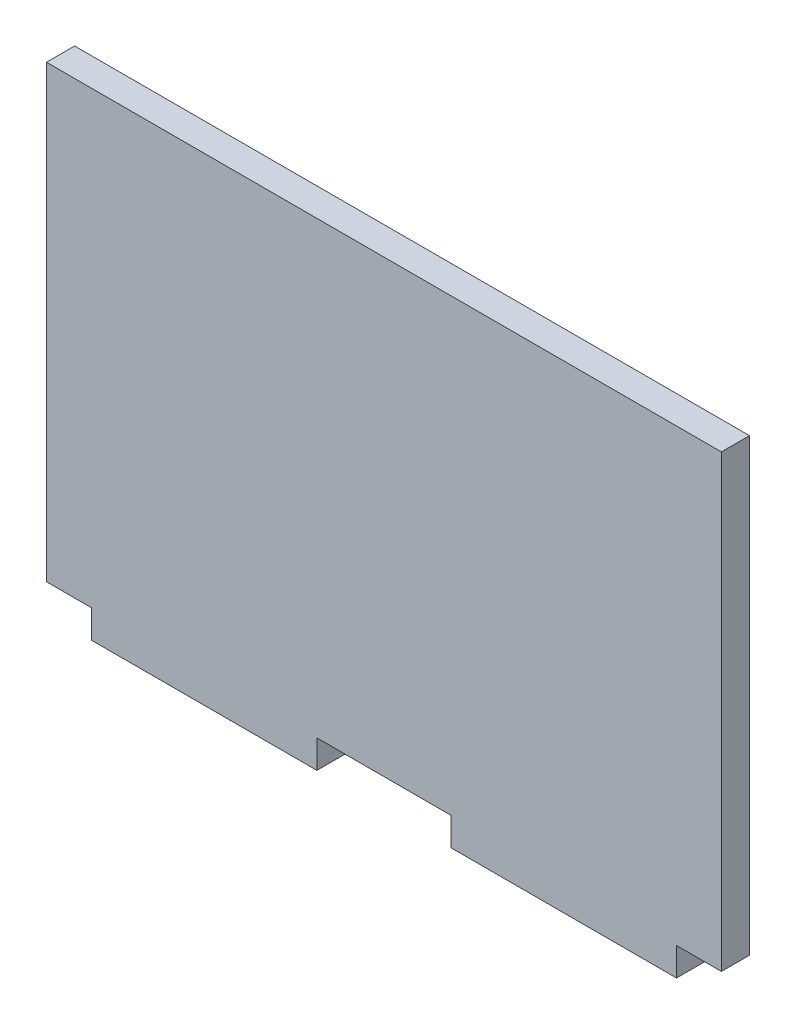
SolidWorks part; units mm, degrees
ref_plane "Front Plane" through (0, 0, 0) normal (0, 0, 1) x (1, 0, 0)
ref_plane "Top Plane" through (0, 0, 0) normal (0, 1, 0) x (1, 0, 0)
ref_plane "Right Plane" through (0, 0, 0) normal (1, 0, 0) x (0, 0, -1)
sketch "Sketch1" plane through (0, 0, 0) normal (0, 0, 1) x (1, 0, 0)
  line L0 (-2.5933, 76.1981) -> (-2.5933, -25.4019) construction
  line L1 (-78.7933, 76.1981) -> (73.6067, 76.1981)
  line L2 (-78.7933, 76.1981) -> (-78.7933, -25.4019)
  line L3 (-78.7933, -25.4019) -> (73.6067, -25.4019)
  line L4 (73.6067, 76.1981) -> (73.6067, -25.4019)
  line L5 (-68.6583, -25.4019) -> (-17.7316, -25.4019)
  line L6 (-68.6583, -25.4019) -> (-68.6583, -31.7519)
  line L7 (-68.6583, -31.7519) -> (-17.7316, -31.7519)
  line L8 (-17.7316, -25.4019) -> (-17.7316, -31.7519)
  line L9 (63.4716, -31.7519) -> (12.5449, -31.7519)
  line L10 (12.5449, -25.4019) -> (12.5449, -31.7519)
  line L11 (63.4716, -25.4019) -> (63.4716, -31.7519)
  dimension "D1" = 101.6
  dimension "D2" = 152.4
  dimension "D3" = 10.135
  dimension "D4" = 50.9267
  dimension "D5" = 6.35
extrude "Boss-Extrude1" add sketch "Sketch1" along normal blind 6.35 contours L0 L1 L2 L3 | L1 L0 L3 L4 | L11 L3 L10 L9 | L8 L3 L6 L7 region at (35.5067, 25.3981, 0) region at (-40.6933, 25.3981, 0) region at (-43.1949, -28.5769, 0) region at (38.0083, -28.5769, 0)
equation "\"width\"= 9in"
equation "\"Height\"= 18in"
equation "\"thick\"= 0.25"
equation "\"D5@Sketch1\"=\"thick\""
equation "\"D1@Boss-Extrude1\"=\"thick\""
